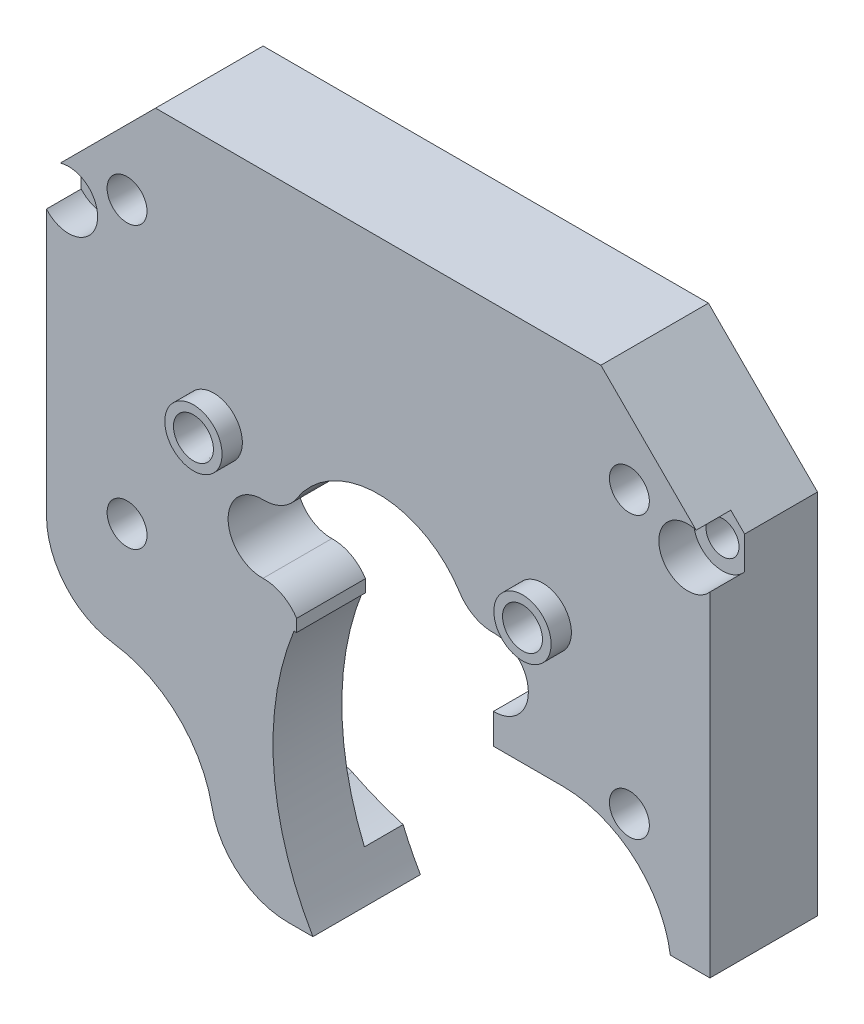
SolidWorks part; units mm, degrees
material "PET"
ref_plane "Front Plane" through (0, 0, 0) normal (0, 0, 1) x (1, 0, 0)
ref_plane "Top Plane" through (0, 0, 0) normal (0, 1, 0) x (1, 0, 0)
ref_plane "Right Plane" through (0, 0, 0) normal (1, 0, 0) x (0, 0, -1)
sketch "Sketch1" plane through (0, 0, 0) normal (0, 0, 1) x (1, 0, 0)
  circle A0 centre (0, 0) radius 24.7015
  circle A1 centre (0, 0) radius 7.9375
  dimension "D1" = 49.403
  dimension "D2" = 15.875
extrude "Boss-Extrude1" add sketch "Sketch1" along normal up to surface (5.65 mm away)
hole_wizard "CBORE SLOT for #2 Pan Head Machine Screw1" positions "Sketch13" profile "Sketch12" size "#2" standard "ANSI Inch" slot yes end condition through all
sketch "Sketch13" plane through (0, 0, 0) normal (0, 0, -1) x (-1, 0, 0)
  line L0 (-2.0066, 13.2132) -> (-2.0066, 19.5632) construction
  line L2 (7.493, 13.2132) -> (7.493, 19.5632) construction
  line L4 (-1.8669, 13.2132) -> (-2.1463, 13.2132) construction
  circle A1 centre (7.493, 14.3181) radius 1.1049 construction
  point P9 (-2.0066, 16.3882)
  point P11 (7.493, 16.3882)
  dimension "D1" = 6.35
sketch "Sketch12" plane through (2.0066, 16.3882, 0) normal (1, 0, 0) x (0, 1, 0)
  line L0 (0, 0) -> (0, 5.65)
  line L1 (0, 5.65) -> (1.3525, 5.65)
  line L3 (1.3525, 5.65) -> (1.3526, 1.5748)
  line L4 (2.3812, 1.5748) -> (1.3526, 1.5748)
  line L5 (2.3812, 1.5748) -> (2.3812, 1.0325)
  line L6 (2.3812, 1.0325) -> (3.4138, 0)
  line L7 (3.4138, 0) -> (0, 0)
  line L8 (-2.3812, 1.0325) -> (-3.4138, 0) construction
  line L11 (0, -6.35) -> (0, 107.95) construction
  dimension "Thru Hole Dia." = 2.7051
  dimension "Thru Hole Depth" = 5.65
  dimension "C'Bore Dia." = 4.7625
  dimension "C'Bore Depth" = 1.5748
  dimension "Near C'Sink Dia." = 6.8275
  dimension "Near C'Sink Angle" = 90
sketch "Sketch11" plane through (0, 0, 5.65) normal (0, 0, 1) x (1, 0, 0)
  line L0 (-24.2881, -4.5) -> (-11.876, -4.5)
  line L1 (-17.5, -4.5) -> (-13.5554, -4.5) construction
  line L2 (0, 0) -> (0, -12.7) construction
  line L3 (24.2881, -4.5) -> (11.876, -4.5)
  arc A0 (-11.876, -4.5) -> (11.876, -4.5) centre (0, 0) ccw
  arc A1 (-24.2881, -4.5) -> (24.2881, -4.5) centre (0, 0) ccw
  circle A2 centre (0, 0) radius 7.9375 construction
  dimension "D1" = 25.4
  dimension "D2" = 49.403
extrude "Boss-Extrude5" add sketch "Sketch11" along normal blind 12.7
sketch "Sketch17" plane through (0, 0, 5.65) normal (0, 0, 1) x (1, 0, 0)
  line L0 (-24.2881, -4.5) -> (-20.4781, -4.5)
  line L1 (-11.876, -4.5) -> (-24.2881, -4.5) construction
  line L2 (-20.4781, -4.5) -> (-20.4781, 4.39)
  line L3 (-13.4931, 20.6906) -> (-13.4931, 4.39) construction
  line L4 (-13.4931, 4.39) -> (-20.4781, 4.39) construction
  line L5 (0, 24.7015) -> (0, 0) construction
  line L6 (13.4931, 4.39) -> (20.4781, 4.39) construction
  line L7 (13.4931, 20.6906) -> (13.4931, 4.39) construction
  line L8 (20.4781, -4.5) -> (20.4781, 4.39)
  line L9 (24.2881, -4.5) -> (20.4781, -4.5)
  line L10 (-13.4931, 16.0175) -> (-13.4931, 20.6906)
  line L11 (13.4931, 16.0175) -> (13.4931, 20.6906)
  arc A0 (-13.4931, 20.6906) -> (-24.2881, -4.5) centre (0, 0) ccw
  arc A1 (24.2881, -4.5) -> (-24.2881, -4.5) centre (0, 0) ccw construction
  arc A2 (13.4931, 20.6906) -> (24.2881, -4.5) centre (0, 0) cw
  arc A3 (-13.4931, 16.0175) -> (-20.4781, 4.39) centre (0, 0) ccw
  arc A4 (20.4781, 4.39) -> (13.4931, 16.0175) centre (0, 0) ccw
  dimension "D1" = 3.81
  dimension "D2" = 6.985
  dimension "D3" = 8.89
extrude "Boss-Extrude7" add sketch "Sketch17" along normal up to surface (12.7 mm away) up to face at (0, -11.6004, 18.35)
sketch "Sketch32" plane through (0, 0, 0) normal (0, 0, -1) x (-1, 0, 0)
  line L0 (-18.3768, 26.4668) -> (18.3768, 26.4668) construction
  line L1 (-27.4725, 17.3712) -> (-18.3768, 26.4668) construction
  line L2 (-27.4725, -17.6276) -> (-27.4725, 17.3712) construction
  line L3 (18.3768, -26.4668) -> (-18.6333, -26.4668) construction
  line L4 (27.4725, -17.3712) -> (18.3768, -26.4668) construction
  line L5 (27.4725, 17.3712) -> (27.4725, -17.3712) construction
  line L6 (18.3768, 26.4668) -> (27.4725, 17.3712) construction
  line L7 (-18.3768, 26.4668) -> (18.3768, 26.4668) construction
  line L8 (-27.4725, 17.3712) -> (-18.3768, 26.4668) construction
  line L9 (-27.4725, -17.6276) -> (-27.4725, 17.3712) construction
  line L10 (18.3768, -26.4668) -> (-18.6333, -26.4668) construction
  line L11 (27.4725, -17.3712) -> (18.3768, -26.4668) construction
  line L12 (27.4725, 17.3712) -> (27.4725, -17.3712) construction
  line L13 (18.3768, 26.4668) -> (27.4725, 17.3712) construction
  line L14 (18.2716, 26.2128) -> (27.2185, 17.266)
  line L15 (27.2185, 17.266) -> (27.2185, -16.7395)
  line L16 (27.2185, -16.7395) -> (29.6895, -16.7395)
  line L17 (16.2895, -26.2128) -> (-18.2716, -26.2128)
  line L18 (-27.2185, -17.266) -> (-27.2185, 17.266)
  line L19 (-27.2185, 17.266) -> (-18.2716, 26.2128)
  line L20 (-18.2716, 26.2128) -> (18.2716, 26.2128)
  line L21 (27.2185, -17.266) -> (18.2716, -26.2128) construction
  line L23 (29.6895, -16.7395) -> (29.6895, -29.2395)
  line L24 (29.6895, -29.2395) -> (16.2895, -29.2395)
  line L25 (16.2895, -29.2395) -> (16.2895, -26.2128)
  line L26 (18.2716, -26.2128) -> (-18.6333, -26.2128) construction
  line L27 (27.2185, 17.266) -> (27.2185, -17.266) construction
  line L28 (-18.2716, -26.2128) -> (-27.2185, -17.266)
  line L29 (-27.2185, -17.6276) -> (-27.2185, 17.266) construction
  arc A0 (-27.4725, -17.6276) -> (-18.6333, -26.4668) centre (-18.6333, -17.6276) ccw construction
  circle A1 centre (0, 0) radius 24.7015
  circle A2 centre (0, 0) radius 24.7015
  arc A3 (-27.4725, -17.6276) -> (-18.6333, -26.4668) centre (-18.6333, -17.6276) ccw construction
  arc A5 (-27.2185, -17.6276) -> (-18.6333, -26.2128) centre (-18.6333, -17.6276) ccw construction
  dimension "D1" = 0
  dimension "D2" = 0.254
extrude "Boss-Extrude8" add sketch "Sketch32" against normal up to surface (18.35 mm away) up to face at (0, 1.1766, 18.35)
sketch "Sketch33" plane through (0, 0, 18.35) normal (0, 0, 1) x (1, 0, 0)
  line L1 (-13.4931, 20.6906) -> (13.4931, 20.6906)
  line L2 (-13.4931, 20.6906) -> (-13.4931, 22.4028)
  line L3 (-13.4931, 26.2128) -> (13.4931, 26.2128)
  line L4 (13.4931, 20.6906) -> (13.4931, 22.4028)
  line L5 (13.4931, 20.6906) -> (13.4931, 16.0175) construction
  line L6 (-18.2716, 26.2128) -> (18.2716, 26.2128) construction
  line L29 (-13.4931, 22.4028) -> (-13.4931, 26.2128)
  line L30 (13.4931, 26.2128) -> (13.4931, 22.4028)
extrude "Cut-Extrude1" cut sketch "Sketch33" against normal up to surface (12.7 mm away) up to face at (-7.9375, 0, 5.65)
sketch "Sketch35" plane through (0, 0, 18.35) normal (0, 0, 1) x (1, 0, 0)
  line L0 (20.4781, 4.39) -> (20.4781, -4.5) construction
  line L1 (13.4931, 26.2128) -> (13.4931, 16.0175) construction
  line L2 (-13.4931, 16.0175) -> (-13.4931, 26.2128) construction
  line L3 (-20.4781, -4.5) -> (-20.4781, 4.39) construction
  line L12 (-20.4781, -4.5) -> (-20.4781, 4.39)
  line L13 (-13.4931, 16.0175) -> (-13.4931, 25.6031)
  line L14 (13.4931, 25.6031) -> (13.4931, 16.0175)
  line L15 (20.4781, 4.39) -> (20.4781, -4.5)
  line L16 (-27.2185, -16.7395) -> (-27.2185, 17.266) construction
  line L17 (-27.2185, 17.266) -> (-18.2716, 26.2128) construction
  line L20 (18.2716, 26.2128) -> (27.2185, 17.266) construction
  line L21 (27.2185, 17.266) -> (27.2185, -17.266) construction
  line L22 (-27.2185, -16.7395) -> (-27.2185, 17.266) construction
  line L23 (-27.2185, 17.266) -> (-18.2716, 26.2128) construction
  line L24 (-23.4085, 15.6878) -> (-15.5775, 23.5187) construction
  line L25 (15.5775, 23.5187) -> (23.4085, 15.6878) construction
  line L26 (18.2716, 26.2128) -> (27.2185, 17.266) construction
  line L27 (27.2185, 17.266) -> (27.2185, -17.266) construction
  line L28 (-23.4085, -4.5) -> (-23.4085, 15.6878)
  line L29 (-23.4085, 15.6878) -> (-13.4931, 25.6031)
  line L30 (13.4931, 25.6031) -> (23.4085, 15.6878)
  line L31 (23.4085, 15.6878) -> (23.4085, -4.5)
  line L32 (-20.4781, -4.5) -> (-23.4085, -4.5)
  line L33 (20.4781, -4.5) -> (23.4085, -4.5)
  line L34 (-23.4085, -16.7395) -> (-23.4085, 15.6878) construction
  line L35 (23.4085, 15.6878) -> (23.4085, -17.266) construction
  arc A0 (20.4781, 4.39) -> (13.4931, 16.0175) centre (0, 0) ccw construction
  arc A1 (-13.4931, 16.0175) -> (-20.4781, 4.39) centre (0, 0) ccw construction
  arc A6 (-13.4931, 16.0175) -> (-20.4781, 4.39) centre (0, 0) ccw
  arc A7 (20.4781, 4.39) -> (13.4931, 16.0175) centre (0, 0) ccw
  dimension "D1" = 3.81
extrude "Cut-Extrude2" cut sketch "Sketch35" against normal up to surface (12.7 mm away) up to face at (-7.9375, 0, 5.65)
sketch "Sketch37" plane through (0, 0, 18.35) normal (0, 0, 1) x (1, 0, 0)
  line L16 (-23.4085, 15.6878) -> (-13.4931, 25.6031)
  line L17 (-13.4931, 25.6031) -> (-13.4931, 26.2128)
  line L18 (-13.4931, 26.2128) -> (-18.2716, 26.2128)
  line L19 (-18.2716, 26.2128) -> (-27.2185, 17.266)
  line L20 (-27.2185, 17.266) -> (-27.2185, -16.7395)
  line L21 (-27.2185, -16.7395) -> (-29.6895, -16.7395)
  line L22 (-16.2895, -26.2128) -> (18.2716, -26.2128)
  line L23 (27.2185, -17.266) -> (27.2185, 17.266)
  line L24 (27.2185, 17.266) -> (18.2716, 26.2128)
  line L25 (18.2716, 26.2128) -> (13.4931, 26.2128)
  line L26 (13.4931, 26.2128) -> (13.4931, 25.6031)
  line L27 (13.4931, 25.6031) -> (23.4085, 15.6878)
  line L28 (23.4085, 15.6878) -> (23.4085, -4.5)
  line L29 (23.4085, -4.5) -> (11.876, -4.5)
  line L30 (-11.876, -4.5) -> (-23.4085, -4.5)
  line L31 (-23.4085, -4.5) -> (-23.4085, 15.6878)
  line L32 (-23.4085, 15.6878) -> (-13.4931, 25.6031)
  line L33 (-13.4931, 25.6031) -> (-13.4931, 26.2128)
  line L34 (-13.4931, 26.2128) -> (-18.2716, 26.2128)
  line L35 (-18.2716, 26.2128) -> (-27.2185, 17.266)
  line L36 (-27.2185, 17.266) -> (-27.2185, -16.7395)
  line L37 (-27.2185, -16.7395) -> (-29.6895, -16.7395)
  line L38 (-16.2895, -26.2128) -> (18.2716, -26.2128)
  line L39 (27.2185, -17.266) -> (27.2185, 17.266)
  line L40 (27.2185, 17.266) -> (18.2716, 26.2128)
  line L41 (18.2716, 26.2128) -> (13.4931, 26.2128)
  line L42 (13.4931, 26.2128) -> (13.4931, 25.6031)
  line L43 (13.4931, 25.6031) -> (23.4085, 15.6878)
  line L44 (23.4085, 15.6878) -> (23.4085, -4.5)
  line L45 (23.4085, -4.5) -> (11.876, -4.5)
  line L46 (-11.876, -4.5) -> (-23.4085, -4.5)
  line L47 (-23.4085, -4.5) -> (-23.4085, 15.6878)
  line L52 (-29.6895, -16.7395) -> (-29.6895, -29.2395)
  line L53 (-29.6895, -16.7395) -> (-29.6895, -29.2395)
  line L54 (-29.6895, -29.2395) -> (-16.2895, -29.2395)
  line L55 (-29.6895, -29.2395) -> (-16.2895, -29.2395)
  line L56 (-16.2895, -29.2395) -> (-16.2895, -26.2128)
  line L57 (-16.2895, -29.2395) -> (-16.2895, -26.2128)
  line L58 (18.2716, -26.2128) -> (27.2185, -17.266)
  line L59 (18.2716, -26.2128) -> (27.2185, -17.266)
  arc A3 (-11.876, -4.5) -> (11.876, -4.5) centre (0, 0) ccw
  arc A5 (-11.876, -4.5) -> (11.876, -4.5) centre (0, 0) ccw
  dimension "D1" = 0
extrude "Cut-Extrude3" cut sketch "Sketch37" against normal up to surface (12.7 mm away) up to face at (-3.5089, 1.6246, 18.35)
hole_wizard "Hole1" positions "Sketch41" profile "Sketch40" legacy
sketch "Sketch41" plane through (0, 0, 5.65) normal (0, 0, 1) x (1, 0, 0)
  line L0 (-14, -4.5) -> (-27.2185, -4.5) construction
  line L1 (-27.2185, 17.266) -> (-27.2185, -16.7395) construction
  line L3 (-20.6092, -4.5) -> (-20.6092, 26.2128) construction
  line L5 (18.2716, 26.2128) -> (-18.2716, 26.2128) construction
  line L6 (-20.6092, 26.2128) -> (-20.6092, 10.8564)
  line L10 (14, -4.5) -> (27.2185, -4.5) construction
  line L11 (27.2185, -17.266) -> (27.2185, 17.266) construction
  point P0 (-20.6092, 18.5346)
  point P3 (-20.6092, -4.5)
  point P6 (20.6092, 18.5346)
  point P57 (20.6092, -4.5)
sketch "Sketch40" plane through (-20.6092, 18.5346, 5.65) normal (1, 0, 0) x (0, -1, 0)
  line L0 (0, 0) -> (0, 2.921)
  line L1 (0, 2.921) -> (1.4986, 2.921)
  line L2 (1.4986, 2.921) -> (1.6383, 0)
  line L3 (1.6383, 0) -> (0, 0)
  line L4 (0, 110) -> (0, -10) construction
  dimension "Minor Diameter" = 2.9972
  dimension "Depth" = 2.921
  dimension "Major Diameter" = 3.2766
hole_wizard "Ø3.0 (3) Diameter Hole1" positions "Sketch43" profile "Sketch42" hole size "Ø3.0" standard "ANSI Metric" end condition through all
sketch "Sketch43" plane through (0, 0, 5.65) normal (0, 0, 1) x (1, 0, 0)
  point P0 (-20.6092, 18.5346)
  point P3 (20.6092, 18.5346)
  point P6 (-20.6092, -4.5)
  point P13 (20.6092, -4.5)
sketch "Sketch42" plane through (-20.6092, 18.5346, 5.65) normal (1, 0, 0) x (0, -1, 0)
  line L0 (0, 0) -> (0, 5.65)
  line L1 (0, 5.65) -> (1.5, 5.65)
  line L2 (1.5, 5.65) -> (1.5, 0)
  line L5 (1.5, 0) -> (0, 0)
  line L11 (0, -6.35) -> (0, 107.95) construction
  dimension "Thru Hole Dia." = 3
  dimension "Thru Hole Depth" = 5.65
sketch "Sketch44" plane through (0, 0, 5.65) normal (0, 0, 1) x (1, 0, 0)
  line L0 (0, 0) -> (0, -7.9375) construction
  circle A0 centre (-9.525, 0) radius 2.794
  circle A1 centre (0, 0) radius 7.9375 construction
  circle A2 centre (9.525, 0) radius 2.794
  dimension "D1" = 5.588
extrude "Cut-Extrude4" cut sketch "Sketch44" against normal through all
fillet "Fillet1" radius 1.27 2 edges at (-16.2895, -26.2128, 2.825) (-27.2185, -16.7395, 2.825)
sketch "Sketch45" plane through (0, 0, 0) normal (0, 0, -1) x (-1, 0, 0)
  line L0 (22.9895, -29.2395) -> (22.9895, -22.9895) construction
  line L1 (16.2895, -29.2395) -> (29.6895, -29.2395) construction
  line L2 (22.9895, -22.9895) -> (29.6895, -22.9895) construction
  line L3 (29.6895, -29.2395) -> (29.6895, -16.7395) construction
  line L5 (19.5254, -16.9895) -> (16.0613, -22.9895)
  line L6 (16.0613, -22.9895) -> (19.5254, -28.9895)
  line L7 (19.5254, -28.9895) -> (26.4536, -28.9895)
  line L8 (26.4536, -28.9895) -> (29.9177, -22.9895)
  line L9 (29.9177, -22.9895) -> (26.4536, -16.9895)
  line L10 (26.4536, -16.9895) -> (19.5254, -16.9895)
  circle A0 centre (22.9895, -22.9895) radius 6 construction
  dimension "D1" = 12
extrude "Cut-Extrude5" cut sketch "Sketch45" against normal through all
sketch "Sketch46" plane through (0, 0, 0) normal (0, 0, -1) x (-1, 0, 0)
  line L14 (19.5254, -16.9895) -> (26.4536, -16.9895)
  line L15 (19.5254, -16.9895) -> (26.4536, -16.9895)
  line L16 (29.6895, -22.5942) -> (29.6895, -16.7395)
  line L17 (27.2185, -15.4695) -> (27.2185, 17.266)
  line L18 (27.2185, 17.266) -> (18.2716, 26.2128)
  line L19 (18.2716, 26.2128) -> (-18.2716, 26.2128)
  line L20 (-18.2716, 26.2128) -> (-27.2185, 17.266)
  line L21 (-27.2185, 17.266) -> (-27.2185, -17.266)
  line L22 (-27.2185, -17.266) -> (-18.2716, -26.2128)
  line L23 (-18.2716, -26.2128) -> (15.0195, -26.2128)
  line L24 (16.2895, -27.4828) -> (16.2895, -29.2395)
  line L25 (16.2895, -29.2395) -> (29.6895, -29.2395)
  line L26 (26.4536, -16.9895) -> (29.6895, -22.5942)
  line L27 (26.4536, -16.9895) -> (29.6895, -22.5942)
  line L28 (19.5254, -28.9895) -> (16.0613, -22.9895)
  line L29 (19.5254, -28.9895) -> (16.0613, -22.9895)
  line L30 (29.6895, -22.5942) -> (29.6895, -16.7395)
  line L31 (27.2185, -15.4695) -> (27.2185, 17.266)
  line L32 (27.2185, 17.266) -> (18.2716, 26.2128)
  line L33 (18.2716, 26.2128) -> (-18.2716, 26.2128)
  line L34 (-18.2716, 26.2128) -> (-27.2185, 17.266)
  line L35 (-27.2185, 17.266) -> (-27.2185, -17.266)
  line L36 (-27.2185, -17.266) -> (-18.2716, -26.2128)
  line L37 (-18.2716, -26.2128) -> (15.0195, -26.2128)
  line L38 (16.2895, -27.4828) -> (16.2895, -29.2395)
  line L39 (16.2895, -29.2395) -> (29.6895, -29.2395)
  line L40 (16.0613, -22.9895) -> (19.5254, -16.9895)
  line L41 (16.0613, -22.9895) -> (19.5254, -16.9895)
  line L46 (29.6895, -16.7395) -> (28.4885, -16.7395)
  line L47 (29.6895, -16.7395) -> (28.4885, -16.7395)
  line L48 (29.6895, -29.2395) -> (29.6895, -23.3847)
  line L49 (29.6895, -29.2395) -> (29.6895, -23.3847)
  line L50 (29.6895, -23.3847) -> (26.4536, -28.9895)
  line L51 (29.6895, -23.3847) -> (26.4536, -28.9895)
  line L52 (26.4536, -28.9895) -> (19.5254, -28.9895)
  line L53 (26.4536, -28.9895) -> (19.5254, -28.9895)
  circle A0 centre (0, 0) radius 23.8252 construction
  circle A1 centre (0, 0) radius 24.3332
  arc A7 (27.2185, -15.4695) -> (28.4885, -16.7395) centre (28.4885, -15.4695) ccw
  arc A8 (16.2895, -27.4828) -> (15.0195, -26.2128) centre (15.0195, -27.4828) ccw
  arc A11 (27.2185, -15.4695) -> (28.4885, -16.7395) centre (28.4885, -15.4695) ccw
  arc A12 (16.2895, -27.4828) -> (15.0195, -26.2128) centre (15.0195, -27.4828) ccw
  dimension "D1" = 47.6504
  dimension "D2" = 0.508
  dimension "D3" = 0
extrude "Boss-Extrude9" add sketch "Sketch46" along normal blind 3.175
fillet "Fillet3" radius 3.175 4 edges at (7.66, 2.0804, 2.825) (7.66, -2.0804, 2.825) (-7.66, -2.0804, 2.825) (-7.66, 2.0804, 2.825)
sketch "Sketch47" plane through (0, 0, 5.65) normal (0, 0, 1) x (1, 0, 0)
  line L0 (-29.6895, -22.5942) -> (-29.6895, -28.9895)
  line L1 (-29.6895, -28.9895) -> (-19.5254, -28.9895)
  line L2 (-29.6895, -22.5942) -> (-26.4536, -16.9895) construction
  line L3 (-26.4536, -16.9895) -> (-19.5254, -16.9895) construction
  line L4 (-19.5254, -16.9895) -> (-16.0613, -22.9895) construction
  line L5 (-16.0613, -22.9895) -> (-19.5254, -28.9895) construction
  line L6 (-29.6895, -22.5942) -> (-26.4536, -16.9895)
  line L7 (-26.4536, -16.9895) -> (-19.5254, -16.9895)
  line L8 (-19.5254, -16.9895) -> (-16.0613, -22.9895)
  line L9 (-16.0613, -22.9895) -> (-19.5254, -28.9895)
extrude "Boss-Extrude10" add sketch "Sketch47" against normal through all
fillet "Fillet2" radius 1.27 3 edges at (-29.6895, -16.7395, 1.2375) (-16.2895, -29.2395, 1.2375) (-29.6895, -29.2395, 1.2375)
sketch "Sketch48" plane through (0, 0, -3.175) normal (0, 0, -1) x (-1, 0, 0)
  circle A0 centre (22.9895, -22.9895) radius 9.525
  dimension "D1" = 19.05
extrude "Cut-Extrude6" cut sketch "Sketch48" against normal through all
fillet "Fillet4" radius 6.35 2 edges at (-14.0264, -26.2128, 1.2375) (-27.2185, -14.4548, 1.2375)
fillet "Fillet5" radius 1.27 2 edges at (-13.9718, -19.9222, -1.5875) (-19.9222, -13.9718, -1.5875)
hole_wizard "CBORE for #2 Pan Head Machine Screw1" positions "Sketch50" profile "Sketch49" counterbore size "#2" standard "ANSI Inch" end condition through all
sketch "Sketch50" plane through (0, 0, 5.65) normal (0, 0, 1) x (1, 0, 0)
  point P0 (-25.4059, 16.1162)
  point P3 (25.4059, 16.1162)
  point P6 (17.2045, -24.6819)
sketch "Sketch49" plane through (-25.4059, 16.1162, 5.65) normal (1, 0, 0) x (0, -1, 0)
  line L0 (0, 0) -> (0, 8.825)
  line L1 (0, 8.825) -> (1.3525, 8.825)
  line L3 (1.3525, 8.825) -> (1.3525, 2.8448)
  line L4 (1.3525, 2.8448) -> (2.3812, 2.8448)
  line L5 (2.3812, 2.8448) -> (2.3812, 0)
  line L7 (2.3812, 0) -> (0, 0)
  line L11 (0, -6.35) -> (0, 107.95) construction
  dimension "Thru Hole Dia." = 2.7051
  dimension "Thru Hole Depth" = 8.825
  dimension "C'Bore Dia." = 4.7625
  dimension "C'Bore Depth" = 2.8448
sketch "Sketch51" plane through (0, 0, -3.175) normal (0, 0, 1) x (1, 0, 0)
  line L0 (-6.9143, -5.2705) -> (15.1765, -5.2705)
  line L1 (8.8903, -20.4467) -> (-1.6615, -30.9985)
  line L2 (15.1765, -14.1605) -> (8.8903, -20.4467) construction
  arc A0 (-6.9143, -5.2705) -> (-1.6615, -30.9985) centre (15.1765, -14.1605) ccw
  arc A1 (8.8903, -20.4467) -> (15.1765, -5.2705) centre (15.1765, -14.1605) ccw
  dimension "D1" = 47.625
  dimension "D2" = 17.78
  dimension "D3" = 45
extrude "Cut-Extrude7" cut sketch "Sketch51" along normal up to next
sketch "Sketch52" plane through (0, 0, 5.65) normal (0, 0, 1) x (1, 0, 0)
  line L0 (27.2185, -17.266) -> (27.2185, 14.5718) construction
  line L1 (9.4546, -2.7931) -> (5.9351, -2.7931)
  line L2 (9.4546, -2.7931) -> (9.4546, -5.2705)
  line L3 (9.4546, -5.2705) -> (5.9351, -5.2705)
  line L4 (5.9351, -2.7931) -> (5.9351, -5.2705)
  line L5 (-5.9351, -5.2705) -> (-6.6961, -5.2705)
  line L6 (-5.9351, -5.2705) -> (-5.9351, -4.2622)
  line L7 (-5.9351, -4.2622) -> (-6.6961, -4.2622)
  line L8 (-6.6961, -5.2705) -> (-6.6961, -4.2622)
  line L9 (27.2185, -12.8586) -> (3.1242, -12.8586)
  line L10 (27.2185, -12.8586) -> (27.2185, -26.2128)
  line L11 (27.2185, -26.2128) -> (3.1242, -26.2128)
  line L12 (3.1242, -12.8586) -> (3.1242, -26.2128)
  line L13 (8.8903, -20.4467) -> (8.8903, -5.2705) construction
  point P22 (8.8903, -12.8586)
extrude "Cut-Extrude8" cut sketch "Sketch52" against normal through all body kept at (18.2716, 26.2128, 5.65)
sketch "Sketch53" plane through (0, 0, 5.65) normal (0, 0, 1) x (1, 0, 0)
  circle A0 centre (13.5, 6) radius 2.35 construction
  circle A1 centre (-13.5, 6) radius 2.35 construction
  circle A2 centre (13.5, 6) radius 2.35
  circle A3 centre (-13.5, 6) radius 2.35
extrude "Boss-Extrude11" add sketch "Sketch53" along normal up to surface (1.663 mm away)
fillet "Fillet6" [suppressed] radius 2.54
sketch "Sketch54" plane through (0, 0, 0) normal (0, 0, -1) x (-1, 0, 0)
  line L2 (1.4072, 14.5658) -> (1.4072, 18.2107)
  line L3 (-5.4204, 18.2107) -> (-5.4204, 14.5658)
  line L4 (1.4072, 14.5658) -> (1.4072, 18.2107)
  line L5 (-5.4204, 18.2107) -> (-5.4204, 14.5658)
  line L6 (4.0792, 18.2107) -> (4.0792, 14.5658)
  line L7 (10.9068, 14.5658) -> (10.9068, 18.2107)
  line L8 (4.0792, 18.2107) -> (4.0792, 14.5658)
  line L9 (10.9068, 14.5658) -> (10.9068, 18.2107)
  arc A3 (1.4072, 18.2107) -> (-5.4204, 18.2107) centre (-2.0066, 18.2107) ccw
  arc A4 (-5.4204, 14.5658) -> (1.4072, 14.5658) centre (-2.0066, 14.5658) ccw
  arc A5 (1.4072, 18.2107) -> (-5.4204, 18.2107) centre (-2.0066, 18.2107) ccw
  arc A6 (-5.4204, 14.5658) -> (1.4072, 14.5658) centre (-2.0066, 14.5658) ccw
  arc A7 (10.9068, 18.2107) -> (4.0792, 18.2107) centre (7.493, 18.2107) ccw
  arc A8 (4.0792, 14.5658) -> (10.9068, 14.5658) centre (7.493, 14.5658) ccw
  arc A9 (10.9068, 18.2107) -> (4.0792, 18.2107) centre (7.493, 18.2107) ccw
  arc A10 (4.0792, 14.5658) -> (10.9068, 14.5658) centre (7.493, 14.5658) ccw
  dimension "D1" = 0
  dimension "D2" = 0
extrude "Boss-Extrude12" add sketch "Sketch54" against normal up to surface (5.65 mm away) up to face at (-15.85, 6, 5.65)
hole_wizard "#0 Clearance Hole1" positions "Sketch55" profile "Sketch56" hole size "#0" standard "ANSI Inch" end condition up to next
sketch "Sketch55" plane through (0, 0, 0) normal (0, 0, -1) x (-1, 0, 0)
  point P0 (-13.5, 6)
  point P3 (13.5, 6)
sketch "Sketch56" plane through (13.5, 6, 0) normal (1, 0, 0) x (0, 1, 0)
  line L0 (0, 0) -> (0, 7.313)
  line L1 (0, 7.313) -> (0.9271, 7.313)
  line L2 (0.9271, 7.313) -> (0.9271, 0)
  line L5 (0.9271, 0) -> (0, 0)
  line L11 (0, -6.35) -> (0, 107.95) construction
  dimension "Thru Hole Dia." = 1.8542
  dimension "Thru Hole Depth" = 7.313
hole_wizard "Hole2" positions "Sketch57" profile "Sketch58" legacy
sketch "Sketch57" plane through (0, 0, 7.313) normal (0, 0, 1) x (1, 0, 0)
  point P0 (-13.5, 6)
  point P3 (13.5, 6)
sketch "Sketch58" plane through (-13.5, 6, 7.313) normal (1, 0, 0) x (0, -1, 0)
  line L0 (0, 0) -> (0, 2.921)
  line L1 (0, 2.921) -> (1.4986, 2.921)
  line L2 (1.4986, 2.921) -> (1.6383, 0)
  line L3 (1.6383, 0) -> (0, 0)
  line L4 (0, 110) -> (0, -10) construction
  dimension "Minor Diameter" = 2.9972
  dimension "Depth" = 2.921
  dimension "Major Diameter" = 3.2766
